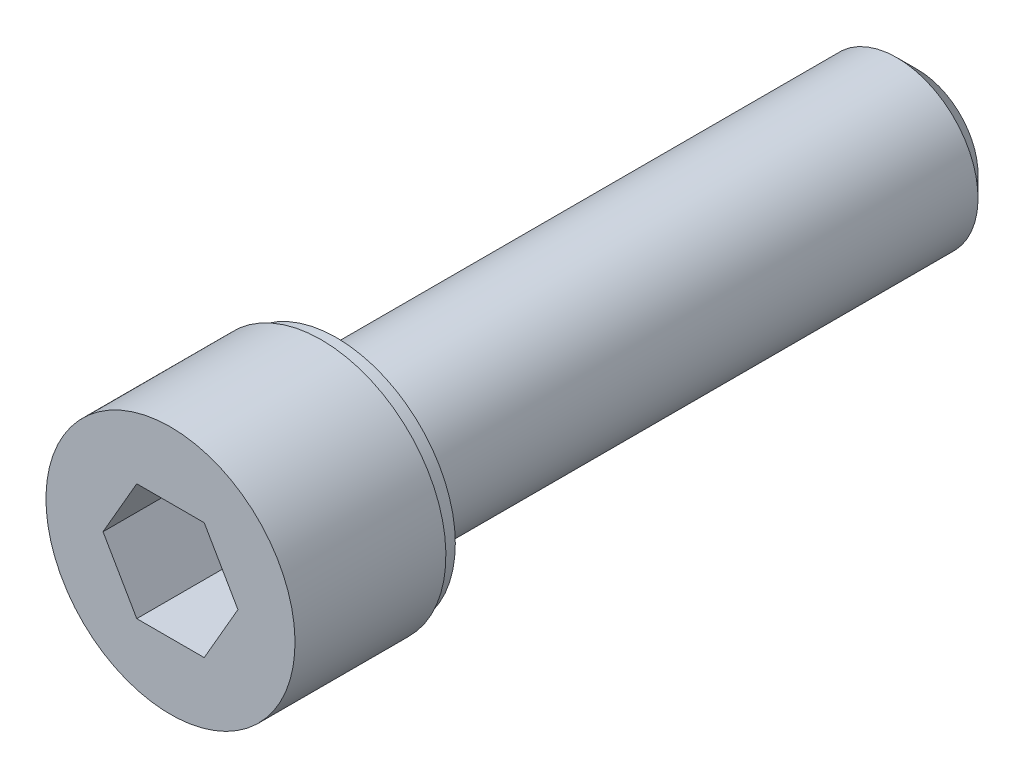
SolidWorks part; units mm, degrees
material "1.4305 (X8CrNiS18-9)"
ref_plane "Front Plane" through (0, 0, 0) normal (0, 0, 1) x (1, 0, 0)
ref_plane "Top Plane" through (0, 0, 0) normal (0, 1, 0) x (1, 0, 0)
ref_plane "Right Plane" through (0, 0, 0) normal (1, 0, 0) x (0, 0, -1)
sketch "Croquis1" plane through (0, 0, 0) normal (1, 0, 0) x (0, 0, -1)
  line L0 (0, 3) -> (3.635, 3)
  line L1 (3.635, 3) -> (3.635, 2.862)
  line L2 (4, 1.955) -> (18, 1.955)
  line L3 (18, 1.955) -> (18, 0)
  line L4 (18, 0) -> (0, 0)
  line L5 (0, 0) -> (0, 3)
  line L6 (3.635, 2.862) -> (4, 2.862)
  line L7 (4, 2.862) -> (4, 1.955)
  dimension "D1" = 4
  dimension "D2" = 14
  dimension "D3" = 1.955
  dimension "D4" = 3
  dimension "D5" = 0.365
  dimension "D6" = 0.138
revolve "Revolución1" add sketch "Croquis1" angle 360 about L4
ref_plane "Plano1" through (0, 0, -1.82) normal (0, 0, 1) x (1, 0, 0)
ref_axis "Eje1" through (0, 0, 2.9752) along (0, 0, -1)
fillet "Redondeo1" radius 0.2 1 edges at (0, 1.955, -4)
chamfer "Chaflán1" distance 0.5 angle 45 1 edges at (0, 1.955, -18)
sketch "Croquis2" plane through (0, 0, 0) normal (0, 0, 1) x (1, 0, 0)
  line L1 (-1.625, 0) -> (-0.8125, -1.4073)
  line L2 (-0.8125, -1.4073) -> (0.8125, -1.4073)
  line L3 (0.8125, -1.4073) -> (1.625, 0)
  line L4 (1.625, 0) -> (0.8125, 1.4073)
  line L5 (0.8125, 1.4073) -> (-0.8125, 1.4073)
  line L6 (-0.8125, 1.4073) -> (-1.625, 0)
  circle A0 centre (0, 0) radius 1.4073 construction
  dimension "D1" = 1.625
extrude "Cortar-Extruir1" cut sketch "Croquis2" against normal blind 2.75
